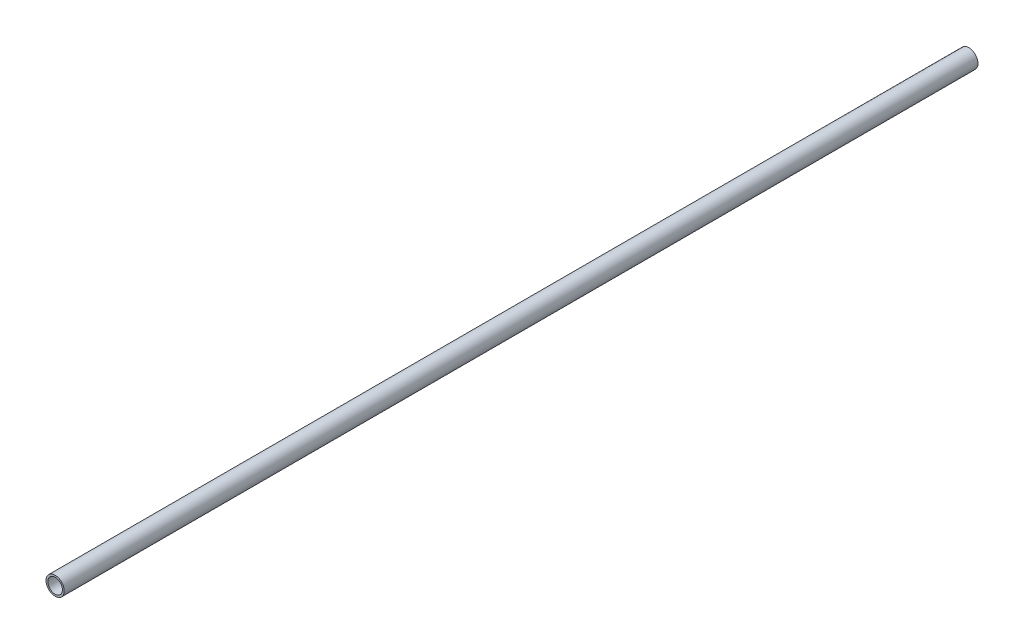
SolidWorks part; units mm, degrees
ref_plane "Front Plane" through (0, 0, 0) normal (0, 0, 1) x (1, 0, 0)
ref_plane "Top Plane" through (0, 0, 0) normal (0, 1, 0) x (1, 0, 0)
ref_plane "Right Plane" through (0, 0, 0) normal (1, 0, 0) x (0, 0, -1)
sketch "Sketch1" plane through (0, 0, 0) normal (0, 0, 1) x (1, 0, 0)
  circle A0 centre (0, 0) radius 5
  circle A1 centre (0, 0) radius 4
  dimension "D1" = 10
  dimension "D2" = 8
extrude "Boss-Extrude1" add sketch "Sketch1" along normal blind 500
